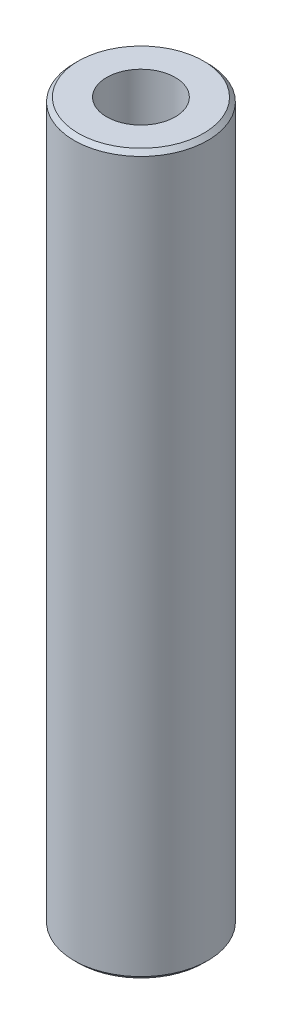
SolidWorks part; units mm, degrees
ref_plane "Front Plane" through (0, 0, 0) normal (0, 0, 1) x (1, 0, 0)
ref_plane "Top Plane" through (0, 0, 0) normal (0, 1, 0) x (1, 0, 0)
ref_plane "Right Plane" through (0, 0, 0) normal (1, 0, 0) x (0, 0, -1)
sketch "Sketch1" plane through (0, 0, 0) normal (0, 1, 0) x (1, 0, 0)
  circle A0 centre (0, 0) radius 47.5
  dimension "SHAFT_OD" = 95
extrude "Boss-Extrude1" add sketch "Sketch1" along normal blind 511.0525
sketch "Sketch2" plane through (0, 0, 0) normal (0, 1, 0) x (1, 0, 0)
  circle A0 centre (0, 0) radius 24.3594
  dimension "BORE_D" = 48.7188
extrude "Cut-Extrude1" cut sketch "Sketch2" along normal through all
chamfer "Chamfer1" distance 2.9458 angle 45 2 edges at (0, 511.0525, 47.5) (0, 0, 47.5)
